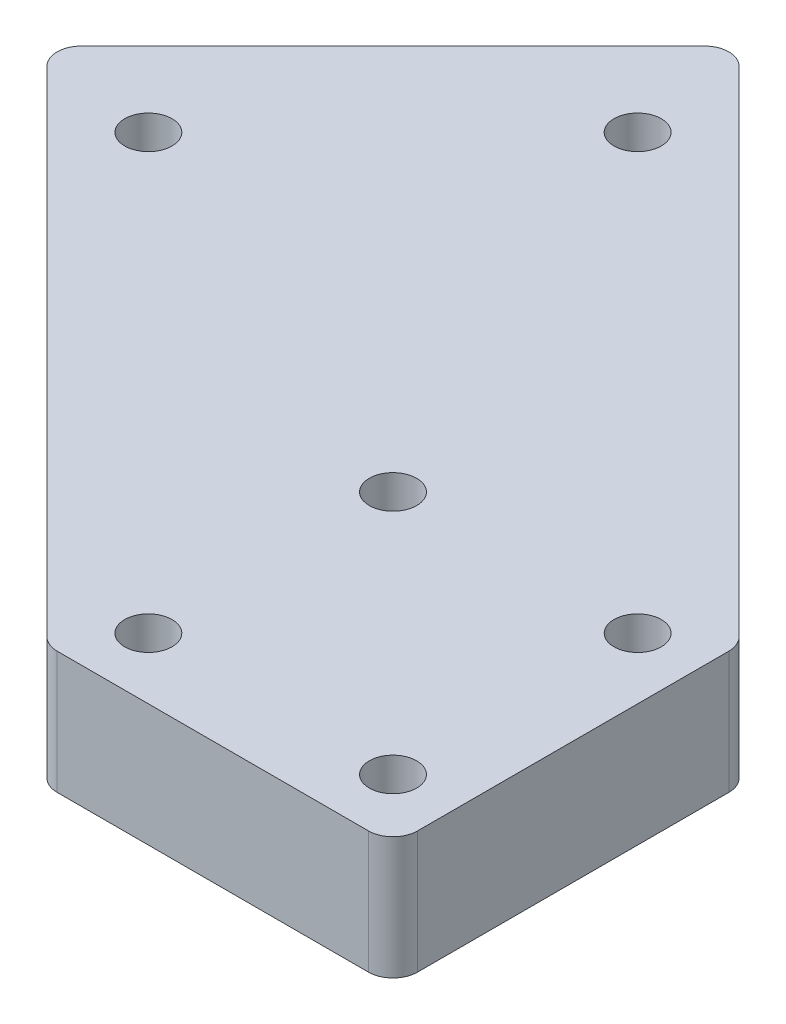
SolidWorks part; units mm, degrees
ref_plane "Front Plane" through (0, 0, 0) normal (0, 0, 1) x (1, 0, 0)
ref_plane "Top Plane" through (0, 0, 0) normal (0, 1, 0) x (1, 0, 0)
ref_plane "Right Plane" through (0, 0, 0) normal (1, 0, 0) x (0, 0, -1)
sketch "Sketch3" plane through (0, 0, 0) normal (0, 1, 0) x (1, 0, 0)
  line L1 (0, 0) -> (35.921, 0)
  line L2 (0, 0) -> (0, -35.921)
  line L3 (0, -35.921) -> (35.921, -35.921)
  line L4 (35.921, 0) -> (35.921, -35.921)
  dimension "D1" = 35.921
extrude "Boss-Extrude2" add sketch "Sketch3" along normal blind 12.7
ref_plane "Plane1" through (0, 0, 0) normal (-0.7071, 0, 0.7071) x (0.7071, 0, 0.7071)
sketch "Sketch4" plane through (0, 0, 0) normal (-0.7071, 0, 0.7071) x (0.7071, 0, 0.7071)
  line L0 (25.4, 12.7) -> (-25.4, 12.7)
  line L1 (0, 0) -> (-50.8, 0)
  line L2 (-25.4, 12.7) -> (-50.8, 12.7)
  line L3 (-50.8, 12.7) -> (-50.8, 0)
  line L4 (0, 0) -> (25.4, 0) construction
  line L5 (0, 0) -> (25.4, 0)
  line L6 (25.4, 0) -> (25.4, 12.7)
  dimension "D1" = 12.7
  dimension "D2" = 25.4
  dimension "D3" = 76.2
extrude "Boss-Extrude3" add sketch "Sketch4" along normal mid plane 50.8
hole_wizard "#8 Clearance Hole1" positions "Sketch5" profile "Sketch6" hole size "#8" standard "ANSI Inch" end condition through all
sketch "Sketch5" plane through (0, 0, 0) normal (0, -1, 0) x (-1, 0, 0)
  line L1 (-29.571, -29.571) -> (-4.171, -29.571)
  line L2 (-29.571, -29.571) -> (-29.571, -4.171)
  line L3 (-29.571, -4.171) -> (-4.171, -4.171)
  line L4 (-4.171, -29.571) -> (-4.171, -4.171)
  line L5 (-38.8909, -38.8909) -> (38.8909, 38.8909) construction
  line L6 (0, -35.921) -> (-35.921, -35.921) construction
  point P2 (-29.571, -29.571)
  point P3 (-4.171, -4.171)
  point P138 (-29.571, -4.171)
  point P139 (-4.171, -29.571)
  dimension "D1" = 6.35
  dimension "D2" = 25.4
sketch "Sketch6" plane through (29.571, 0, 29.571) normal (1, 0, 0) x (0, 0, -1)
  line L0 (0, 0) -> (0, 12.7)
  line L1 (0, 12.7) -> (2.4574, 12.7)
  line L2 (2.4574, 12.7) -> (2.4574, 0)
  line L5 (2.4574, 0) -> (0, 0)
  line L11 (0, -6.35) -> (0, 107.95) construction
  dimension "Thru Hole Dia." = 4.9149
  dimension "Thru Hole Depth" = 12.7
sketch "Sketch7" plane through (0, 12.7, 0) normal (0, 1, 0) x (1, 0, 0)
  line L0 (-38.8909, 38.8909) -> (38.8909, -38.8909) construction
  line L1 (4.171, -4.171) -> (-28.1579, 28.1579) construction
  line L2 (-40.856, 15.4598) -> (-15.4598, 40.856) construction
  circle A2 centre (4.171, -4.171) radius 2.4574 construction
  circle A3 centre (4.171, -4.171) radius 2.4574 construction
  point P4 (-15.4598, 40.856)
  point P13 (-40.856, 15.4598)
  dimension "D1" = 45.72
  dimension "D2" = 35.9156
hole_wizard "#8 Clearance Hole2" positions "Sketch8" profile "Sketch9" hole size "#8" standard "ANSI Inch" end condition through all
sketch "Sketch8" plane through (0, 12.7, 0) normal (0, 1, 0) x (1, 0, 0)
  point P0 (-40.856, 15.4598)
  point P3 (-15.4598, 40.856)
sketch "Sketch9" plane through (-40.856, 12.7, -15.4598) normal (1, 0, 0) x (0, 0, 1)
  line L0 (0, 0) -> (0, 12.7)
  line L1 (0, 12.7) -> (2.4574, 12.7)
  line L2 (2.4574, 12.7) -> (2.4574, 0)
  line L5 (2.4574, 0) -> (0, 0)
  line L11 (0, -6.35) -> (0, 107.95) construction
  dimension "Thru Hole Dia." = 4.9149
  dimension "Thru Hole Depth" = 12.7
sketch "Sketch10" plane through (0, 0, 0) normal (0, -1, 0) x (1, 0, 0)
  circle A0 centre (-40.856, -15.4598) radius 3.937
  circle A1 centre (-15.4598, -40.856) radius 3.937
  dimension "D1" = 7.874
extrude "Cut-Extrude1" cut sketch "Sketch10" against normal blind 6.35
fillet "Fillet1" radius 2.54 5 edges at (-17.9605, 6.35, -53.8815) (-53.8815, 6.35, -17.9605) (35.921, 6.35, 0) (35.921, 6.35, 35.921) (0, 6.35, 35.921)
equation "\"D1@Boss-Extrude3\"=sqr(2 )"
equation "\"D1@Sketch3\"=sqr(2)"
